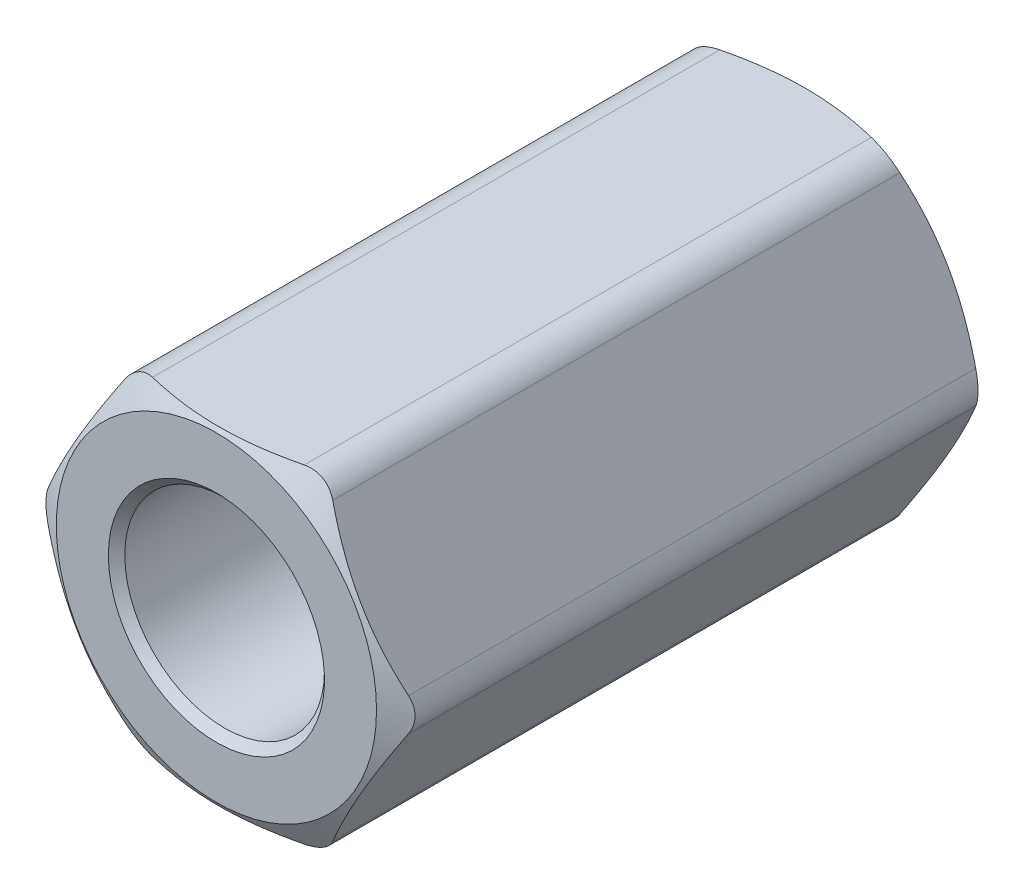
SolidWorks part; units mm, degrees
material "6061-T6 (SS)"
ref_plane "Front Plane" through (0, 0, 0) normal (0, 0, 1) x (1, 0, 0)
ref_plane "Top Plane" through (0, 0, 0) normal (0, 1, 0) x (1, 0, 0)
ref_plane "Right Plane" through (0, 0, 0) normal (1, 0, 0) x (0, 0, -1)
sketch "Sketch1" plane through (0, 0, 0) normal (0, 0, 1) x (1, 0, 0)
  line L1 (2.2914, -3.9688) -> (4.5827, 0)
  line L2 (4.5827, 0) -> (2.2914, 3.9687)
  line L3 (2.2914, 3.9687) -> (-2.2914, 3.9687)
  line L4 (-2.2914, 3.9687) -> (-4.5827, 0)
  line L5 (-4.5827, 0) -> (-2.2914, -3.9688)
  line L6 (-2.2914, -3.9688) -> (2.2914, -3.9688)
  circle A0 centre (0, 0) radius 3.9688 construction
  point P10 (0, -3.9688)
  dimension "Hex Size" = 7.9375
sketch "Sketch2" plane through (0, 0, 0) normal (1, 0, 0) x (0, 0, -1)
  line L0 (7.1437, 0) -> (-7.1437, 0) construction
  line L3 (7.1437, 2.413) -> (7.1437, -2.413) construction
  line L4 (-7.8879, 2.4989) -> (-7.491, 1.8115) construction
  line L5 (-7.491, 1.8115) -> (-7.0941, 2.4989) construction
  line L6 (-7.0941, 2.4989) -> (-7.8879, 2.4989) construction
  line L7 (-7.8383, 2.413) -> (-7.1437, 2.413) construction
  line L8 (-7.5406, 1.8974) -> (-7.4414, 1.8974) construction
  line L9 (-7.491, 1.8974) -> (-7.491, 1.8115) construction
  line L10 (-7.491, 2.413) -> (-7.491, 2.4989) construction
  line L11 (7.1437, 3.9688) -> (-7.1437, 3.9687) construction
  point P6 (0, 3.9688)
  point P9 (7.1437, 0)
  dimension "Thread Length" = 14.2875
  dimension "Thread Size" = 4.826
  dimension "Thread Pitch" = 0.7937
  dimension "Thread Pitch (B)/8" = 0.0992
  dimension "Length" = 14.2875
sketch "Sketch3" plane through (0, 0, 0) normal (1, 0, 0) x (0, 0, -1)
  line L2 (7.1437, 3.9688) -> (7.1437, 2.6114)
  line L3 (7.1437, 2.6114) -> (6.9453, 2.413)
  line L6 (7.1437, 3.9688) -> (7.1437, 2.6114)
  line L8 (6.9453, 2.413) -> (-6.9453, 2.413)
  line L9 (-6.9453, 2.413) -> (-7.1438, 2.6114)
  line L10 (0, 3.9688) -> (7.1437, 3.9688)
  line L11 (-7.1438, 2.6114) -> (-7.1438, 3.9688)
  line L12 (-7.1438, 3.9688) -> (0, 3.9688)
  point P5 (-7.1438, -3.9688)
  dimension "D2" = 0.1984
  dimension "D1" = 45
revolve "Revolve1" add sketch "Sketch3" angle 360 about L0
sketch "Sketch4" plane through (0, 0, 0) normal (0, 0, 1) x (1, 0, 0)
  line L0 (0, 3.9688) -> (0, 2.413) construction
  line L1 (-2.2914, 3.9687) -> (-4.5827, 0)
  line L2 (-4.5827, 0) -> (-2.2914, -3.9688)
  line L3 (-2.2914, -3.9688) -> (2.2914, -3.9688)
  line L4 (2.2914, -3.9688) -> (4.5827, 0)
  line L5 (4.5827, 0) -> (2.2914, 3.9687)
  line L6 (2.2914, 3.9687) -> (-2.2914, 3.9687)
  line L7 (2.2914, -3.9688) -> (4.5827, 0) construction
  circle A0 centre (0, 0) radius 3.9688 construction
  circle A1 centre (0, 0) radius 3.1909
  circle A2 centre (0, 0) radius 3.9688 construction
  point P16 (0, 3.1909)
extrude "Boss-Extrude1" add sketch "Sketch4" against normal mid plane 14.2875
sketch "Sketch5" plane through (0, 0, 7.1438) normal (0, 0, 1) x (1, 0, 0)
  line L0 (0, 2.413) -> (0, -2.413) construction
  line L1 (0, 2.413) -> (0, -2.413) construction
  circle A0 centre (0, 0) radius 3.8695
  point P11 (0, -2.413)
  dimension "D1" = 7.7391
extrude "Cut-Extrude1" cut sketch "Sketch5" against normal through all draft 60 flip side to cut
sketch "Sketch6" plane through (0, 0, -7.1437) normal (0, 0, -1) x (-1, 0, 0)
  circle A0 centre (0, 0) radius 3.8695
  circle A1 centre (0, 0) radius 3.8695 construction
extrude "Cut-Extrude2" cut sketch "Sketch6" against normal through all draft 60 flip side to cut
fillet "Fillet1" radius 0.7937 6 edges at (2.2914, 3.9687, 0) (-4.5827, 0, 0) (-2.2914, -3.9688, 0) (2.2914, -3.9688, 0) (4.5827, 0, 0) (-2.2914, 3.9687, 0)
sketch "Drawing 1" plane through (0, 0, 0) normal (1, 0, 0) x (0, 0, -1)
  line L0 (7.1437, -2.413) -> (-7.1438, -2.413) construction
  line L1 (7.1437, 2.413) -> (-7.1438, 2.413) construction
  line L3 (7.1437, 0) -> (-7.1437, 0) construction
sketch "Sketch7" [suppressed] plane through (0, 0, -7.1437) normal (0, 0, -1) x (-1, 0, 0)
  circle A0 centre (0, 0) radius 2.6114
extrude "Boss-Extrude2" [suppressed] add sketch "Sketch7" along normal up to surface (14.2875 mm away) up to face at (-2.6114, 0, 7.1438)
sketch "Sketch8" [suppressed] plane through (0, 0, 0) normal (1, 0, 0) x (0, 0, -1)
  line L0 (7.1437, 0) -> (-7.1437, 0) construction
  line L1 (7.1437, 2.413) -> (-7.1437, 2.413)
  line L2 (7.1437, 2.413) -> (7.1437, 0)
  line L3 (7.1437, 0) -> (-7.1437, 0)
  line L4 (-7.1437, 2.413) -> (-7.1437, 0)
revolve "Revolve2" [suppressed] add sketch "Sketch8" angle 360 about L0
sketch "Sketch9" [suppressed] plane through (0, 0, 7.1437) normal (0, 0, 1) x (1, 0, 0)
  circle A0 centre (0, 0) radius 2.413
  circle A1 centre (0, 0) radius 2.413 construction
sketch "Sketch10" [suppressed] plane through (0, 0, 0) normal (1, 0, 0) x (0, 0, -1)
  line L0 (-7.5406, 1.8974) -> (-7.4414, 1.8974)
  line L1 (-7.4414, 1.8974) -> (-7.1189, 2.456)
  line L2 (-7.491, 1.8115) -> (-7.0941, 2.4989) construction
  line L3 (-7.1189, 2.456) -> (-7.8631, 2.456)
  line L4 (-7.8879, 2.4989) -> (-7.491, 1.8115) construction
  line L5 (-7.8631, 2.456) -> (-7.5406, 1.8974)
  line L6 (-7.491, 2.413) -> (-7.491, 2.4989) construction
  point P12 (-7.491, 2.456)
curve "Helix/Spiral1" [suppressed] pitch 0.7937 height 11.9062 turns 15
sweep "Cut-Sweep1" [suppressed] cut profiles "Sketch10" path "Helix/Spiral1"
pattern_linear "LPattern1" [suppressed] count 2 spacing 10.3187 of bodies 114
combine bodies "Combine1" [suppressed] operation type subtract main body 113 bodies to subtract 119
ref_plane "Plane1" [suppressed] through (0, 0, 6.9453) normal (0, 0, 1) x (1, 0, 0)
sketch "Sketch11" [suppressed] plane through (0, 0, 7.1438) normal (0, 0, 1) x (1, 0, 0)
  circle A0 centre (0, 0) radius 2.6114
extrude "Cut-Extrude3" [suppressed] cut sketch "Sketch11" against normal through all draft 45
sketch "Sketch12" [suppressed] plane through (0, 0, 6.9453) normal (0, 0, 1) x (1, 0, 0)
  circle A0 centre (0, 0) radius 2.4638
  circle A1 centre (0, 0) radius 2.413 construction
  dimension "D1" = 0.0508
extrude "Cut-Extrude4" [suppressed] cut sketch "Sketch12" against normal through all draft 45
mirror "Mirror1" [suppressed] about plane through (0, 0, 0) normal (0, 0, 1)
equation "\"Thread Pitch (B)/8@Sketch2\" = \"Thread Pitch@Sketch2\" / 8"
equation "\"D1@Fillet1\" = \"Hex Size@Sketch1\" * .1"
equation "\"D3@Helix/Spiral1\"= \"segment length\" + \"Thread Pitch@Sketch2\""
equation "\"D4@Helix/Spiral1\" = \"Thread Pitch@Sketch2\""
equation "\"Thread Length@Sketch2\"=\"Length@Sketch2\""
equation "\"D1@Boss-Extrude1\" = \"Length@Sketch2\""
equation "\"D2@Sketch3\"=\"Thread Pitch@Sketch2\"*.25"
equation "\"D1@Sketch5\"=\"Hex Size@Sketch1\"*.975"
equation "\"thread count\"= \"Length@Sketch2\" * .75 / \"Thread Pitch@Sketch2\""
equation "\"rounded thread count\"= IIF ( \"thread count\" - int ( \"thread count\" ) > 0 , int ( \"thread count\" ) + 1 , \"thread count\" )"
equation "\"segment length\"= \"Thread Pitch@Sketch2\" * \"rounded thread count\""
equation "\"D3@LPattern1\"= \"segment length\" - \"thread pitch@sketch2\""
